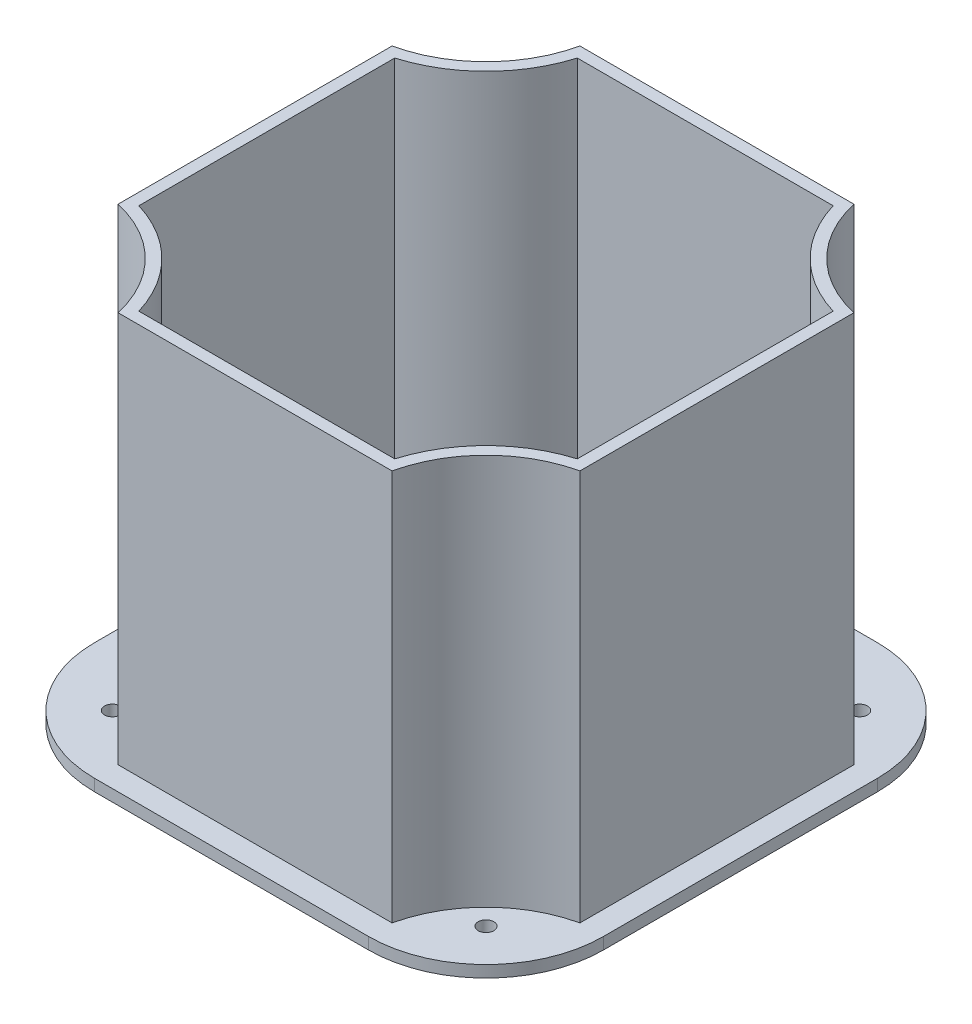
SolidWorks part; units mm, degrees
ref_plane "Front Plane" through (0, 0, 0) normal (0, 0, 1) x (1, 0, 0)
ref_plane "Top Plane" through (0, 0, 0) normal (0, 1, 0) x (1, 0, 0)
ref_plane "Right Plane" through (0, 0, 0) normal (1, 0, 0) x (0, 0, -1)
sketch "Sketch1" plane through (0, 0, 0) normal (0, 1, 0) x (1, 0, 0)
  line L0 (18.5352, -28.169) -> (-16.4648, -28.169)
  line L1 (-16.4648, 30.831) -> (18.5352, 30.831)
  line L2 (-28.4648, 18.831) -> (-28.4648, -16.169)
  line L3 (30.5352, -16.169) -> (30.5352, 18.831)
  line L4 (33.5352, -16.169) -> (33.5352, 18.831)
  line L5 (18.5352, 33.831) -> (-16.4648, 33.831)
  line L6 (-31.4648, 18.831) -> (-31.4648, -16.169)
  line L7 (-16.4648, -31.169) -> (18.5352, -31.169)
  arc A0 (-28.4648, 18.831) -> (-16.4648, 30.831) centre (-31.9312, 34.2975) ccw
  arc A1 (-16.4648, -28.169) -> (-28.4648, -16.169) centre (-31.9312, -31.6354) ccw
  arc A2 (30.5352, -16.169) -> (18.5352, -28.169) centre (34.0017, -31.6354) ccw
  arc A3 (18.5352, 30.831) -> (30.5352, 18.831) centre (34.0017, 34.2975) ccw
  arc A4 (18.5352, -31.169) -> (33.5352, -16.169) centre (18.5352, -16.169) ccw
  arc A5 (33.5352, 18.831) -> (18.5352, 33.831) centre (18.5352, 18.831) ccw
  arc A6 (-16.4648, 33.831) -> (-31.4648, 18.831) centre (-16.4648, 18.831) ccw
  arc A7 (-31.4648, -16.169) -> (-16.4648, -31.169) centre (-16.4648, -16.169) ccw
  circle A8 centre (24.8992, -22.5329) radius 1
  circle A9 centre (-22.8287, -22.5329) radius 1
  circle A10 centre (-22.8287, 25.195) radius 1
  circle A11 centre (24.8992, 25.195) radius 1
extrude "Boss-Extrude1" add sketch "Sketch1" along normal blind 1.5
sketch "Sketch2" plane through (0, 1.5, 0) normal (0, 1, 0) x (1, 0, 0)
  line L4 (-28.4648, 18.831) -> (-28.4648, -16.169) construction
  line L5 (-16.4648, -28.169) -> (18.5352, -28.169) construction
  line L6 (30.5352, -16.169) -> (30.5352, 18.831) construction
  line L7 (18.5352, 30.831) -> (-16.4648, 30.831) construction
  line L8 (29.0352, -15.0113) -> (29.0352, 17.6733)
  line L9 (-15.3071, -26.669) -> (17.3776, -26.669)
  line L10 (-26.9648, 17.6733) -> (-26.9648, -15.0113)
  line L11 (17.3776, 29.331) -> (-15.3071, 29.331)
  line L12 (29.0352, -15.0113) -> (29.0352, 17.6733)
  line L13 (-15.3071, -26.669) -> (17.3776, -26.669)
  line L14 (-26.9648, 17.6733) -> (-26.9648, -15.0113)
  line L15 (17.3776, 29.331) -> (-15.3071, 29.331)
  line L16 (-28.4648, 18.831) -> (-28.4648, -16.169)
  line L17 (-16.4648, -28.169) -> (18.5352, -28.169)
  line L18 (30.5352, -16.169) -> (30.5352, 18.831)
  line L19 (18.5352, 30.831) -> (-16.4648, 30.831)
  arc A4 (-16.4648, -28.169) -> (-28.4648, -16.169) centre (-31.9312, -31.6354) ccw construction
  arc A5 (30.5352, -16.169) -> (18.5352, -28.169) centre (34.0017, -31.6354) ccw construction
  arc A6 (18.5352, 30.831) -> (30.5352, 18.831) centre (34.0017, 34.2975) ccw construction
  arc A7 (-28.4648, 18.831) -> (-16.4648, 30.831) centre (-31.9312, 34.2975) ccw construction
  arc A8 (29.0352, -15.0113) -> (17.3776, -26.669) centre (34.0017, -31.6354) ccw
  arc A9 (-15.3071, -26.669) -> (-26.9648, -15.0113) centre (-31.9312, -31.6354) ccw
  arc A10 (-26.9648, 17.6733) -> (-15.3071, 29.331) centre (-31.9312, 34.2975) ccw
  arc A11 (17.3776, 29.331) -> (29.0352, 17.6733) centre (34.0017, 34.2975) ccw
  arc A12 (29.0352, -15.0113) -> (17.3776, -26.669) centre (34.0017, -31.6354) ccw
  arc A13 (-15.3071, -26.669) -> (-26.9648, -15.0113) centre (-31.9312, -31.6354) ccw
  arc A14 (-26.9648, 17.6733) -> (-15.3071, 29.331) centre (-31.9312, 34.2975) ccw
  arc A15 (17.3776, 29.331) -> (29.0352, 17.6733) centre (34.0017, 34.2975) ccw
  arc A16 (-16.4648, -28.169) -> (-28.4648, -16.169) centre (-31.9312, -31.6354) ccw
  arc A17 (30.5352, -16.169) -> (18.5352, -28.169) centre (34.0017, -31.6354) ccw
  arc A18 (18.5352, 30.831) -> (30.5352, 18.831) centre (34.0017, 34.2975) ccw
  arc A19 (-28.4648, 18.831) -> (-16.4648, 30.831) centre (-31.9312, 34.2975) ccw
  dimension "D1" = 1.5
extrude "Boss-Extrude2" add sketch "Sketch2" against normal up to surface (1.5 mm away) and the other way blind 50 up to face at (1.0352, 0, -1.331)
